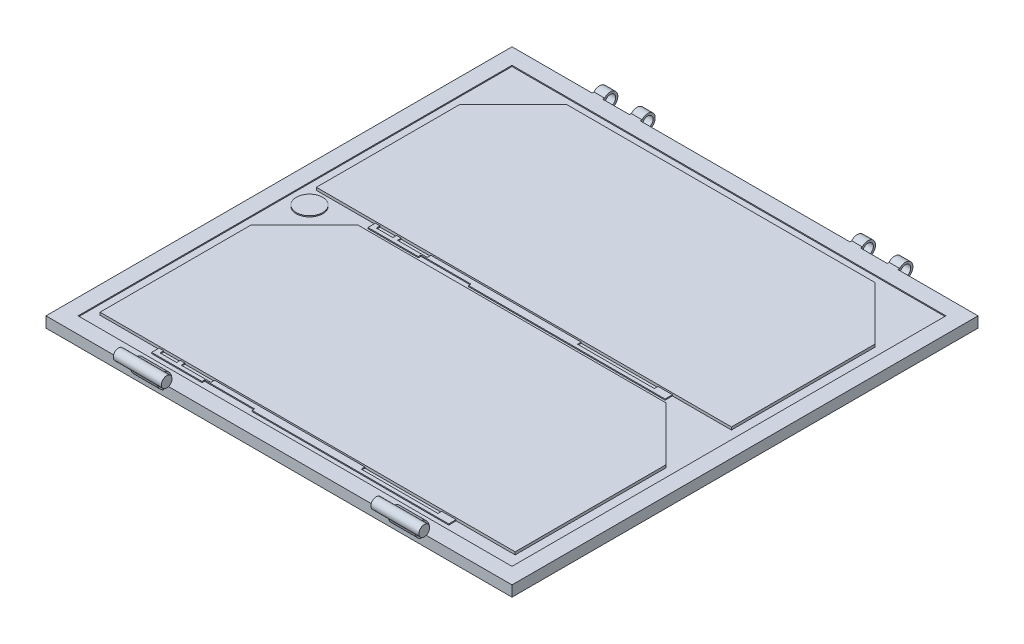
SolidWorks part; units mm, degrees
ref_plane "Front Plane" through (0, 0, 0) normal (0, 0, 1) x (1, 0, 0)
ref_plane "Top Plane" through (0, 0, 0) normal (0, 1, 0) x (1, 0, 0)
ref_plane "Right Plane" through (0, 0, 0) normal (1, 0, 0) x (0, 0, -1)
sketch "Sketch1" plane through (0, 0, 0) normal (0, 1, 0) x (1, 0, 0)
  line L1 (43.6214, -43.6214) -> (-43.6214, -43.6214)
  line L2 (43.6214, -43.6214) -> (43.6214, 43.6214)
  line L3 (43.6214, 43.6214) -> (-43.6214, 43.6214)
  line L4 (-43.6214, -43.6214) -> (-43.6214, 43.6214)
  line L5 (43.6214, -43.6214) -> (-43.6214, 43.6214) construction
  line L6 (43.6214, 43.6214) -> (-43.6214, -43.6214) construction
  circle A0 centre (0, 0) radius 38
extrude "Boss-Extrude1" add sketch "Sketch1" along normal blind 2 contours L3 L4 L1 L2
sketch "Sketch2" plane through (-43.6214, 0, 0) normal (-1, 0, 0) x (0, 0, 1)
  circle A0 centre (-45.0302, 1.0744) radius 1.4088
extrude "Boss-Extrude2" add sketch "Sketch2" against normal blind 2 from offset 15 separate body offset against normal yes
sketch "Sketch3" plane through (-28.6214, 0, 0) normal (-1, 0, 0) x (0, 0, 1)
  circle A0 centre (-45.0302, 1.0744) radius 1
sketch "Sketch4" plane through (-28.6214, 0, 0) normal (-1, 0, 0) x (0, 0, 1)
  line L0 (-43.2204, 0) -> (-44.5765, 0)
  line L1 (43.6214, 0) -> (-43.6214, 0) construction
  line L2 (-43.2204, 2) -> (-44.6517, 2)
  line L3 (43.6214, 2) -> (-43.6214, 2) construction
  line L4 (-44.6517, 2) -> (-44.5765, 0)
  line L5 (-43.2204, 2) -> (-43.2204, 0)
  circle A0 centre (-45.0302, 1.0744) radius 1 construction
extrude "Boss-Extrude3" add sketch "Sketch4" against normal blind 2
sketch "Sketch6" plane through (-26.6214, 0, 0) normal (1, 0, 0) x (0, 0, -1)
  line L0 (43.6214, 2) -> (43.9681, 2)
  line L1 (43.6214, 2) -> (43.9681, 2) construction
  line L2 (43.6214, 0) -> (43.6214, 2) construction
  line L3 (43.6214, 2) -> (43.6214, 0)
  line L4 (43.6214, 0) -> (44.119, 0)
  arc A0 (44.119, 0) -> (43.9681, 2) centre (45.0302, 1.0744) ccw
extrude "Boss-Extrude4" add sketch "Sketch6" along normal blind 2 from offset 5
sketch "Sketch8" plane through (43.6214, 0, 0) normal (1, 0, 0) x (0, 0, -1)
  line L0 (43.9681, 2) -> (43.6214, 2)
  line L1 (43.6214, 2) -> (43.6214, 0)
  line L2 (43.6214, 0) -> (44.119, 0)
  arc A0 (44.119, 0) -> (43.9681, 2) centre (45.0302, 1.0744) ccw
extrude "Boss-Extrude5" add sketch "Sketch8" against normal blind 2 from offset 15 offset against normal yes
sketch "Sketch9" plane through (26.6214, 0, 0) normal (-1, 0, 0) x (0, 0, 1)
  line L0 (-43.9681, 2) -> (-43.6214, 2)
  line L1 (-43.6214, 2) -> (-43.6214, 0)
  line L2 (-44.119, 0) -> (-43.6214, 0) construction
  line L3 (-43.6214, 0) -> (-43.6214, 2) construction
  line L4 (-43.6214, 0) -> (-44.119, 0)
  arc A0 (-43.9681, 2) -> (-44.119, 0) centre (-45.0302, 1.0744) ccw
extrude "Boss-Extrude6" add sketch "Sketch9" along normal blind 2 from offset 5
extrude "Cut-Extrude1" cut sketch "Sketch3" against normal blind 92 contours A0
sketch "Sketch10" plane through (0, 2, 0) normal (0, 1, 0) x (1, 0, 0)
  line L54 (40.6214, 40.6214) -> (-40.6214, 40.6214)
  line L55 (40.6214, 40.6214) -> (-40.6214, 40.6214)
  line L60 (-40.6214, 40.6214) -> (-40.6214, -40.6214)
  line L61 (-40.6214, -40.6214) -> (40.6214, -40.6214)
  line L62 (40.6214, -40.6214) -> (40.6214, 40.6214)
  line L64 (-40.6214, 40.6214) -> (-40.6214, -40.6214)
  line L65 (-40.6214, -40.6214) -> (40.6214, -40.6214)
  line L66 (40.6214, -40.6214) -> (40.6214, 40.6214)
  dimension "D1" = 3
extrude "Cut-Extrude2" cut sketch "Sketch10" against normal blind 0.2
sketch "Sketch11" plane through (0, 1.8, 0) normal (0, 1, 0) x (1, 0, 0)
  line L1 (38.8561, 39.0792) -> (-38.8561, 39.0792)
  line L2 (38.8561, 39.0792) -> (38.8561, 2.2297)
  line L3 (38.8561, 2.2297) -> (-38.8561, 2.2297)
  line L4 (-38.8561, 39.0792) -> (-38.8561, 2.2297)
  line L5 (38.8561, 39.0792) -> (-38.8561, 2.2297) construction
  line L6 (38.8561, 2.2297) -> (-38.8561, 39.0792) construction
  line L7 (38.8561, -38.2682) -> (-38.8561, -38.2682)
  line L8 (38.8561, -38.2682) -> (38.8561, 0)
  line L9 (38.8561, 0) -> (-38.8561, 0)
  line L10 (-38.8561, -38.2682) -> (-38.8561, 0)
  line L11 (38.8561, -38.2682) -> (-38.8561, 0) construction
  line L12 (38.8561, 0) -> (-38.8561, -38.2682) construction
  point P0 (0, 20.6544)
  point P5 (0, -19.1341)
extrude "Boss-Extrude7" add sketch "Sketch11" along normal blind 0.5
chamfer "Chamfer1" distance 10 angle 45 4 edges at (38.8561, 2.05, 0) (-38.8561, 2.05, 0) (38.8561, 2.05, -39.0792) (-38.8561, 2.05, -39.0792)
sketch "Sketch12" plane through (0, 1.8, 0) normal (0, 1, 0) x (1, 0, 0)
  line L0 (-38.8561, 2.2297) -> (38.8561, 2.2297) construction
  line L1 (27.8133, 0.8453) -> (-8.9831, 0.8453)
  line L2 (27.8133, 0.8453) -> (27.8133, 2.2297)
  line L3 (27.8133, 2.2297) -> (25.1091, 2.2297)
  line L4 (-27.8133, 0.8453) -> (-27.8133, 2.2297)
  line L6 (27.8133, 2.2297) -> (25.1091, 2.1624) construction
  line L7 (10.7335, 2.2297) -> (-17.4042, 2.2297)
  line L9 (-26.9367, 2.2297) -> (-26.9367, 1.5375)
  line L10 (-26.9367, 1.5375) -> (-23.843, 1.5375)
  line L11 (-23.843, 2.2297) -> (-23.843, 1.5375)
  line L15 (-22.9642, 2.2297) -> (-22.9642, 1.5375)
  line L16 (-22.9642, 1.5375) -> (-17.4042, 1.5375)
  line L17 (-17.4042, 2.2297) -> (-17.4042, 1.5375)
  line L18 (-26.9367, 2.2297) -> (-27.8133, 2.2297)
  line L19 (-26.9367, 2.2079) -> (-27.8133, 2.2297) construction
  line L20 (-18.3781, 0.8453) -> (-27.8133, 0.8453)
  line L21 (-18.3781, 0.8453) -> (-18.3781, 1.314)
  line L22 (-18.3781, 1.314) -> (-8.9831, 1.314)
  line L23 (-8.9831, 0.8453) -> (-8.9831, 1.314)
  line L27 (10.7335, 2.2297) -> (10.7335, 1.5375)
  line L28 (10.7335, 1.5375) -> (25.1091, 1.5375)
  line L29 (25.1091, 2.2297) -> (25.1091, 1.5375)
  line L30 (-22.9642, 2.2297) -> (-23.843, 2.2297)
  line L32 (-22.9642, 2.109) -> (-23.843, 2.1309) construction
  point P0 (0, 1.5375)
  point P7 (-25.3899, 3.6579)
  point P12 (-20.1842, 3.6579)
  point P17 (-13.6806, -0.4859)
  point P22 (17.9213, 5.7783)
extrude "Boss-Extrude8" add sketch "Sketch12" along normal blind 0.2
pattern_linear "LPattern2" count 2 spacing 40.5 along (0, 0, 1) of "Boss-Extrude8"
sketch "Sketch13" plane through (0, 1.8, 0) normal (0, 1, 0) x (1, 0, 0)
  circle A0 centre (-36.9385, -0.9703) radius 2.4757
extrude "Boss-Extrude9" add sketch "Sketch13" along normal blind 0.2
ref_plane "Plane1" through (0, 1, 0) normal (0, 1, 0) x (1, 0, 0)
mirror "Mirror3" about plane through (0, 1, 0) normal (0, 1, 0) of "Cut-Extrude2"
mirror "Mirror4" about plane through (0, 1, 0) normal (0, 1, 0) of "Boss-Extrude9", "Boss-Extrude7", "LPattern2"
chamfer "Chamfer2" distance 10 angle 45 4 edges at (38.8561, -0.05, -39.0792) (-38.8561, -0.05, -39.0792) (-38.8561, -0.15, 0) (38.8561, -0.05, 0)
sketch "Sketch15" plane through (43.6214, 0, 0) normal (1, 0, 0) x (0, 0, -1)
  line L0 (-43.6214, 1) -> (-45.0314, 1) construction
  line L1 (-43.6214, 2) -> (-43.6214, 0) construction
  line L2 (-45.0314, 1) -> (-45.0314, 4) construction
  circle A0 centre (-45.0314, 4) radius 1
extrude "Boss-Extrude10" add sketch "Sketch15" against normal blind 9 from offset 15 separate body offset against normal yes
sketch "Sketch16" plane through (0, 2, 0) normal (0, 1, 0) x (1, 0, 0)
  line L0 (26.6214, 46.439) -> (26.6214, -49.7129) construction
  line L1 (21.6214, 46.439) -> (21.6214, -49.7129) construction
  line L2 (-26.6214, 46.0302) -> (-26.6214, -47.0906) construction
  line L3 (-26.6214, 44.0302) -> (-26.6214, 46.0302) construction
  line L4 (-26.6214, 43.9681) -> (-26.6214, 46.439) construction
  line L5 (-21.6214, 46.439) -> (-21.6214, -49.7129) construction
sketch "Sketch17" plane through (-43.6214, 0, 0) normal (-1, 0, 0) x (0, 0, 1)
  circle A0 centre (45.0314, 4) radius 1
extrude "Boss-Extrude11" add sketch "Sketch17" against normal blind 9 from offset 15 separate body offset against normal yes
sketch "Sketch18" plane through (0, 2, 0) normal (0, 1, 0) x (1, 0, 0)
  line L0 (-21.6214, 46.439) -> (-21.6214, -49.7129) construction
  line L1 (21.6214, 46.439) -> (21.6214, -49.7129) construction
  line L2 (-26.6214, -42.054) -> (-26.6214, -44.8269)
  line L3 (-26.6214, -44.8269) -> (-21.6214, -44.8269)
  line L4 (-21.6214, -42.054) -> (-21.6214, -44.8269)
  line L5 (-24.1214, -42.054) -> (-21.6214, -44.8269) construction
  line L6 (-26.6214, -44.8269) -> (-24.1214, -42.054) construction
  line L7 (-26.6214, -42.054) -> (-21.6214, -42.054)
  line L8 (21.6214, -42.054) -> (26.6214, -42.054)
  line L9 (21.6214, -42.054) -> (21.6214, -44.8269)
  line L10 (21.6214, -44.8269) -> (26.6214, -44.8269)
  line L11 (26.6214, -42.054) -> (26.6214, -44.8269)
  line L12 (26.6214, 46.439) -> (26.6214, -49.7129) construction
  point P0 (-24.1214, -42.054)
extrude "Boss-Extrude12" add sketch "Sketch18" along normal blind 2 and the other way blind 1
fillet "Fillet1" radius 2 4 edges at (-24.1214, 4, 42.054) (24.1214, 4, 42.054) (24.1214, 1, 44.8269) (-24.1214, 1, 44.8269)
equation "\"z\"=10"
equation "\"2.00mmz\"=2"
